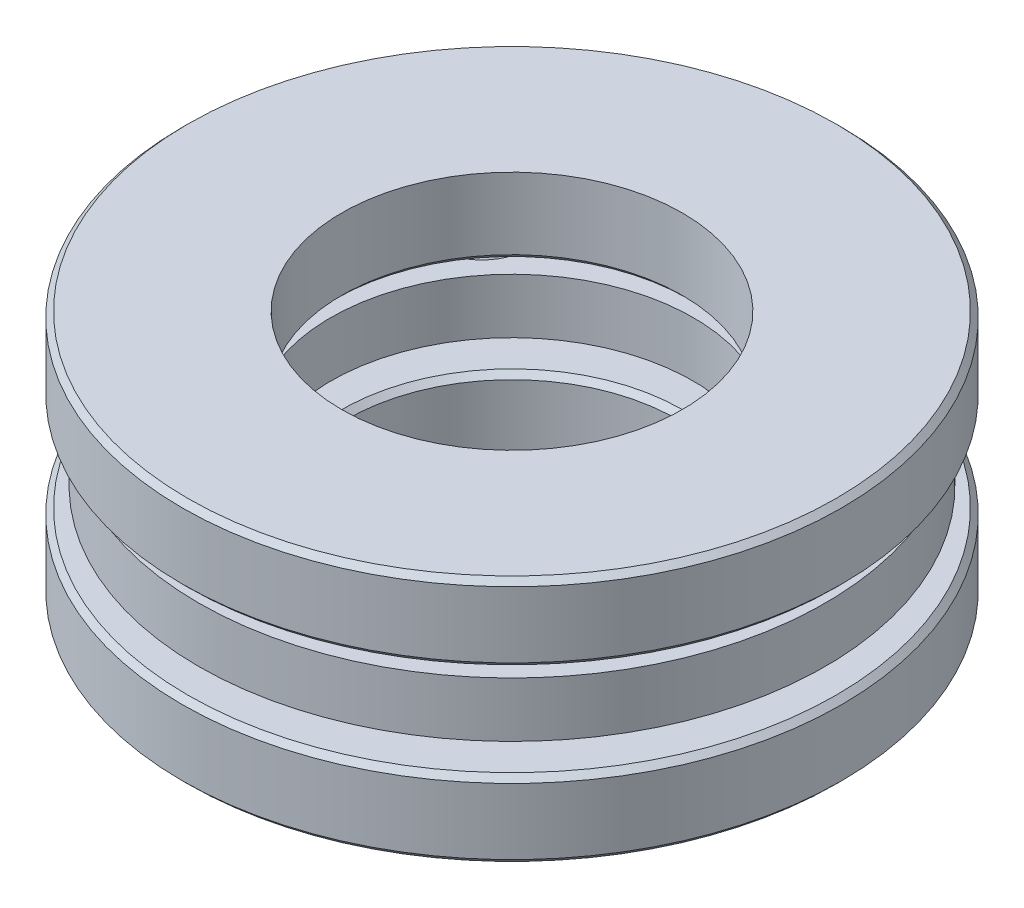
SolidWorks part; units mm, degrees
material "201 Annealed Stainless Steel (SS)"
ref_plane "前视基准面" through (0, 0, 0) normal (0, 0, 1) x (1, 0, 0)
ref_plane "上视基准面" through (0, 0, 0) normal (0, 1, 0) x (1, 0, 0)
ref_plane "右视基准面" through (0, 0, 0) normal (1, 0, 0) x (0, 0, -1)
sketch "Sketch1" plane through (0, 0, 0) normal (0, 1, 0) x (1, 0, 0)
  circle A0 centre (0, 0) radius 6
  circle A1 centre (0, 0) radius 3
  dimension "外径" = 12
  dimension "内径" = 6
extrude "Boss-Extrude1" add sketch "Sketch1" along normal blind 1.4
ref_plane "Top plane" through (0, 4.5, 0) normal (0, 1, 0) x (1, 0, 0)
sketch "Sketch3" plane through (0, 4.5, 0) normal (0, 1, 0) x (1, 0, 0)
  circle A0 centre (0, 0) radius 6
  circle A1 centre (0, 0) radius 3.1
  circle A2 centre (0, 0) radius 6 construction
  circle A3 centre (0, 0) radius 3 construction
  dimension "D1" = 0.1
extrude "Boss-Extrude2" add sketch "Sketch3" against normal blind 1.4
ref_plane "Mid plane" through (0, 2.25, 0) normal (0, 1, 0) x (1, 0, 0)
sketch "Sketch5" plane through (0, 2.25, 0) normal (0, 1, 0) x (1, 0, 0)
  circle A0 centre (0, 0) radius 5.7
  circle A1 centre (0, 0) radius 3.3
  dimension "中圈外径" = 11.4
  dimension "中圈内外差" = 2.4
extrude "Boss-Extrude4" add sketch "Sketch5" along normal mid plane 1
sketch "Sketch2" plane through (0, 2.25, 0) normal (0, 1, 0) x (1, 0, 0)
  line L0 (-4.5, 1) -> (-4.5, -1) construction
  line L1 (-4.5, 1) -> (-4.5, -1)
  arc A0 (-4.5, 1) -> (-4.5, -1) centre (-4.5, 0) ccw
  arc A1 (-4.5, -1) -> (-4.5, 1) centre (-4.5, 0) ccw construction
  point P5 (-4.5, 0)
  dimension "滚子直径" = 2
  dimension "滚子中心半径" = 4.5
revolve "Cut-Revolve1" cut sketch "Sketch2" angle 360 about L0
revolve "Revolve1" add sketch "Sketch2<3>" angle 360 about L0
sketch "Sketch2<3>" plane through (0, 2.25, 0) normal (0, 1, 0) x (1, 0, 0) same geometry as "Sketch2"
pattern_circular "CirPattern2" count 9 over 360 about axis through (0, 1.4, 0) along (0, -1, 0) of "Cut-Revolve1", "Revolve1"
chamfer "Chamfer1" distance 0.1 angle 45 6 edges at (0, 1.4, 3) (0, 3.1, 3.1) (0, 1.4, 6) (0, 3.1, 6) (0, 0, 6) (0, 4.5, 6)
other "冻结***"
